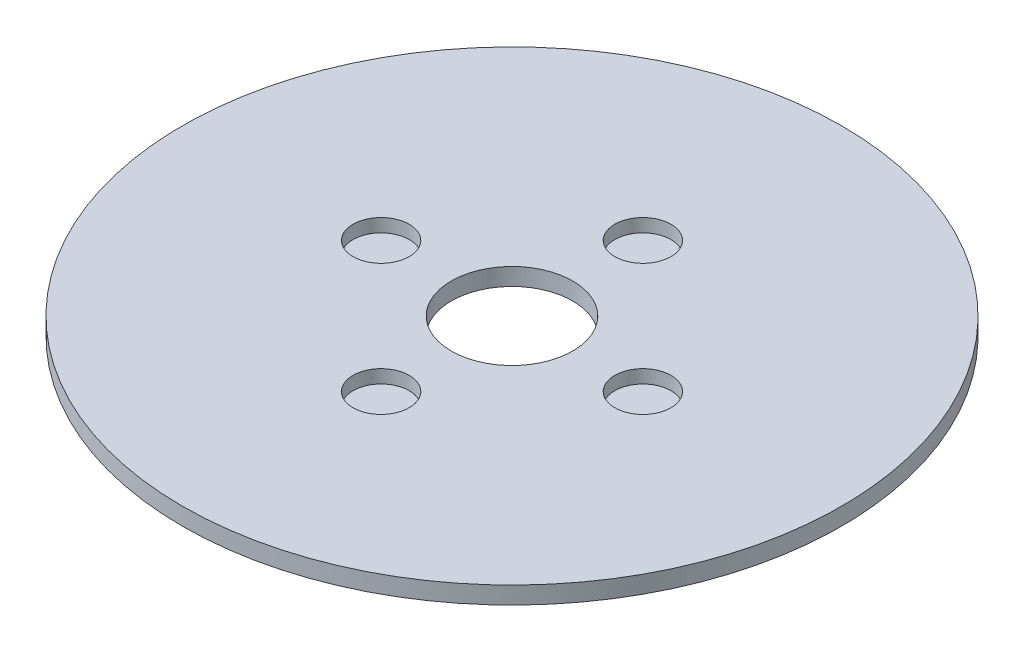
SolidWorks part; units mm, degrees
ref_plane "Front Plane" through (0, 0, 0) normal (0, 0, 1) x (1, 0, 0)
ref_plane "Top Plane" through (0, 0, 0) normal (0, 1, 0) x (1, 0, 0)
ref_plane "Right Plane" through (0, 0, 0) normal (1, 0, 0) x (0, 0, -1)
sketch "Sketch1" plane through (0, 0, 0) normal (0, 1, 0) x (1, 0, 0)
  circle A0 centre (0, 0) radius 95
  dimension "FLANGE_OD" = 190
extrude "Boss-Extrude1" add sketch "Sketch1" along normal blind 5
sketch "Sketch2" plane through (0, 0, 0) normal (0, 1, 0) x (1, 0, 0)
  circle A0 centre (0, 0) radius 17.5
  dimension "BORE_D" = 35
extrude "Cut-Extrude1" cut sketch "Sketch2" along normal through all
sketch "Sketch3" plane through (0, 5, 0) normal (0, 1, 0) x (1, 0, 0)
  circle A0 centre (0, 0) radius 37.7273 construction
  circle A1 centre (-37.7273, 0) radius 8.094
  dimension "BOLT_D" = 16.188
  dimension "BOLT_PCD" = 75.4547
extrude "Cut-Extrude2" cut sketch "Sketch3" against normal blind 3.8345
pattern_circular "CirPattern1" count 4 over 360 about axis through (0, 0, 0) along (0, 1, 0) of "Cut-Extrude2"
